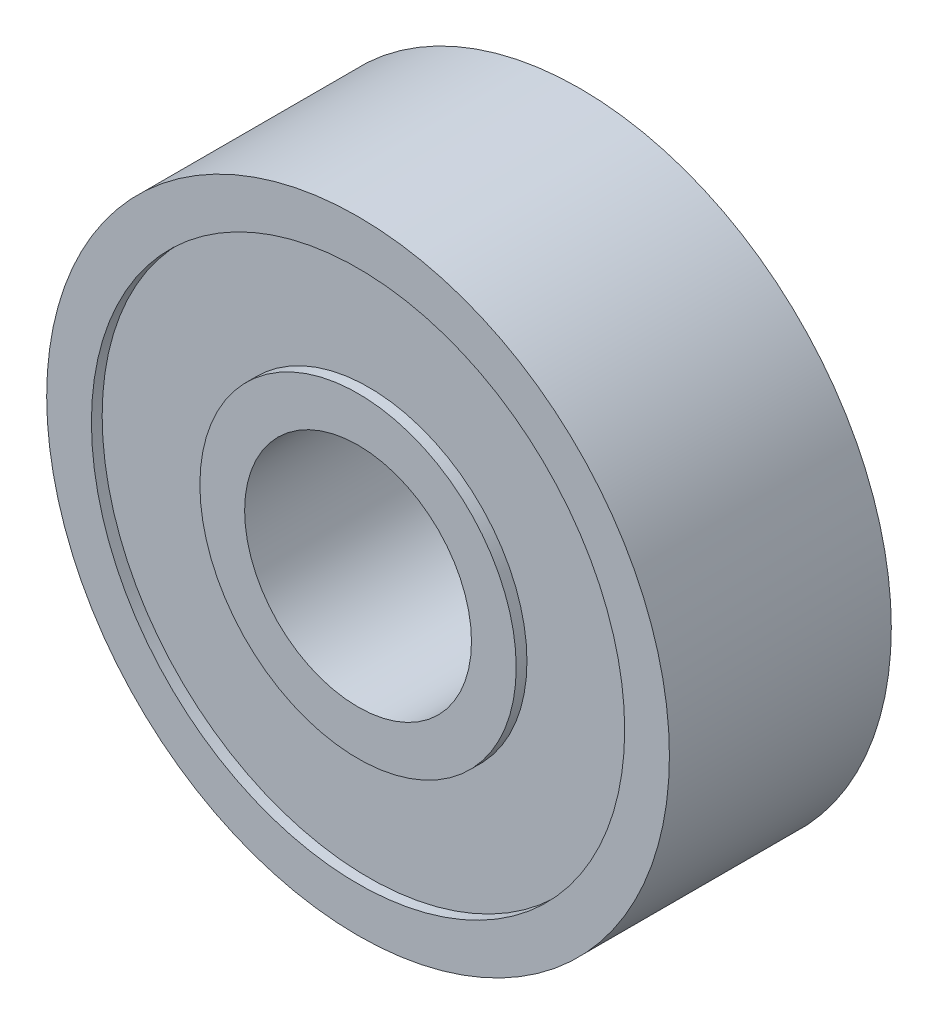
SolidWorks part; units mm, degrees
ref_plane "Front Plane" through (0, 0, 0) normal (0, 0, 1) x (1, 0, 0)
ref_plane "Top Plane" through (0, 0, 0) normal (0, 1, 0) x (1, 0, 0)
ref_plane "Right Plane" through (0, 0, 0) normal (1, 0, 0) x (0, 0, -1)
sketch "Sketch1" plane through (0, 0, 0) normal (0, 0, 1) x (1, 0, 0)
  circle A0 centre (0, 0) radius 4.025
  circle A1 centre (0, 0) radius 11.049
  dimension "D1" = 8.05
  dimension "D2" = 22.098
extrude "Boss-Extrude1" add sketch "Sketch1" along normal mid plane 7.874
sketch "Sketch2" plane through (0, 0, 3.937) normal (0, 0, 1) x (1, 0, 0)
  circle A0 centre (0, 0) radius 9.4615
  circle A1 centre (0, 0) radius 5.6125
  circle A2 centre (0, 0) radius 4.025 construction
  circle A3 centre (0, 0) radius 11.049 construction
  dimension "D1" = 1.5875
  dimension "D2" = 1.5875
extrude "Cut-Extrude1" cut sketch "Sketch2" against normal blind 0.381
mirror "Mirror1" about plane through (0, 0, 0) normal (0, 0, 1) of "Cut-Extrude1"
